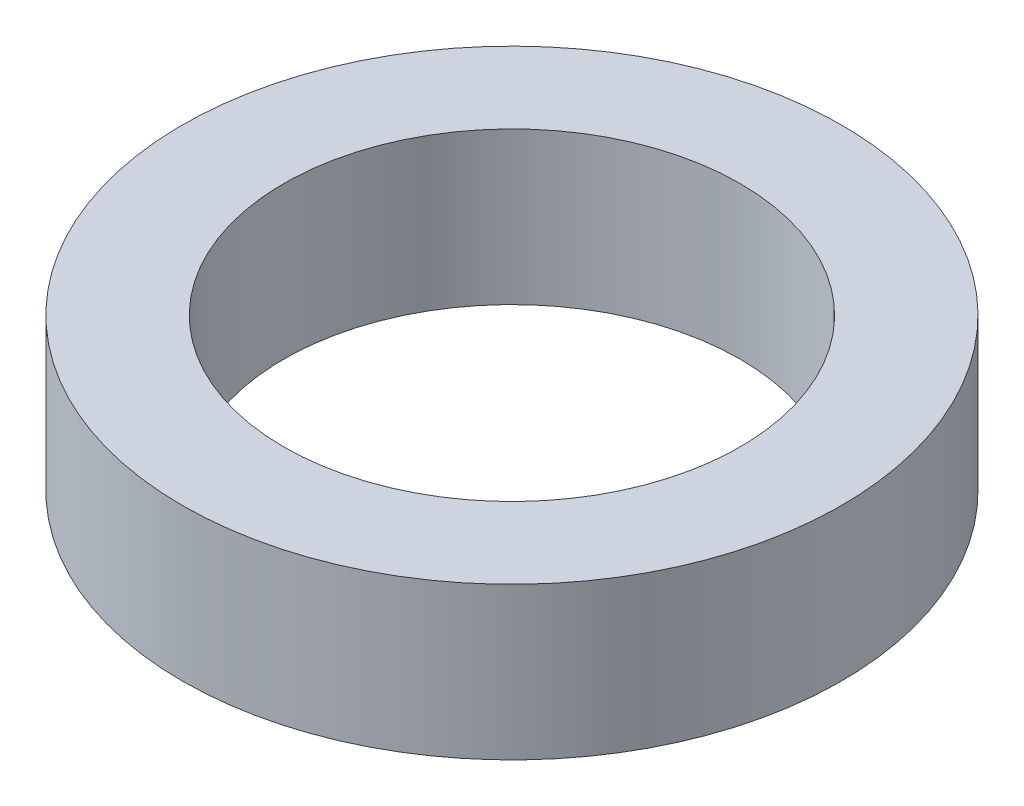
SolidWorks part; units mm, degrees
ref_plane "Plan de face" through (0, 0, 0) normal (0, 0, 1) x (1, 0, 0)
ref_plane "Plan de dessus" through (0, 0, 0) normal (0, 1, 0) x (1, 0, 0)
ref_plane "Plan de droite" through (0, 0, 0) normal (1, 0, 0) x (0, 0, -1)
sketch "Esquisse1" plane through (0, 0, 0) normal (0, 1, 0) x (1, 0, 0)
  circle A0 centre (0, 0) radius 2.25
  circle A1 centre (0, 0) radius 3.25
  dimension "D1" = 4.5
  dimension "D2" = 6.5
extrude "Boss.-Extru.1" add sketch "Esquisse1" along normal blind 1.5
